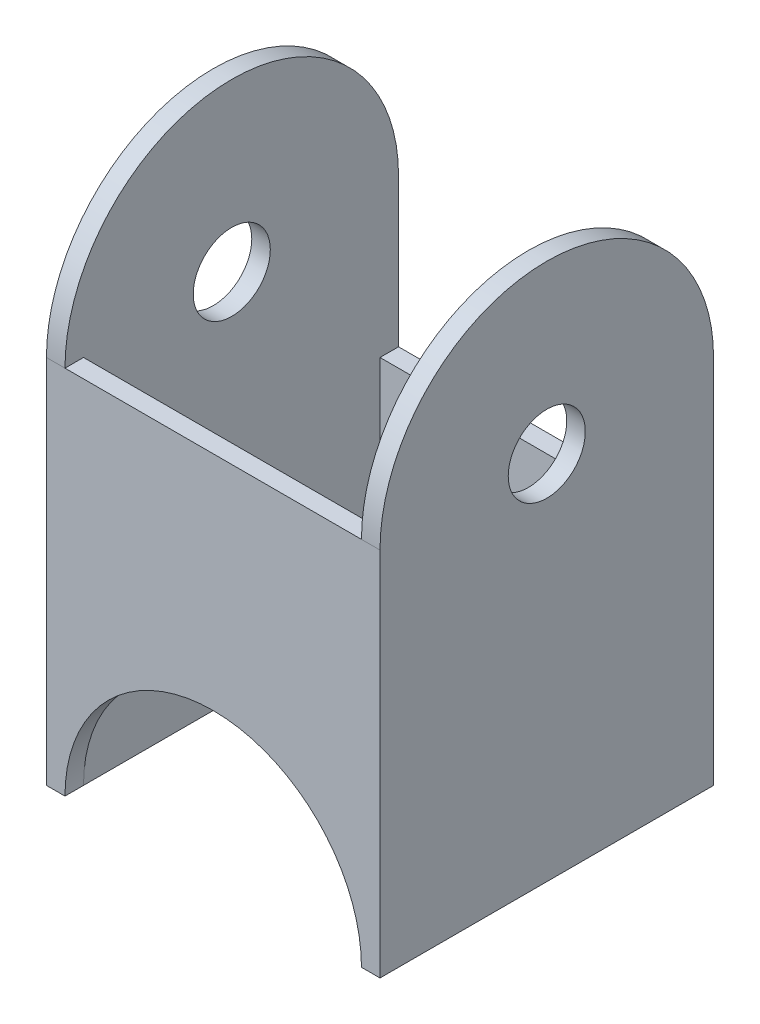
SolidWorks part; units mm, degrees
material "AISI 4130 Steel, annealed at 865C"
ref_plane "Front Plane" through (0, 0, 0) normal (0, 0, 1) x (1, 0, 0)
ref_plane "Top Plane" through (0, 0, 0) normal (0, 1, 0) x (1, 0, 0)
ref_plane "Right Plane" through (0, 0, 0) normal (1, 0, 0) x (0, 0, -1)
sketch "Sketch1" plane through (0, 0, 0) normal (0, 1, 0) x (1, 0, 0)
  line L1 (-12.7, 12.7) -> (12.7, 12.7)
  line L2 (-12.7, 12.7) -> (-12.7, -12.7)
  line L3 (-12.7, -12.7) -> (12.7, -12.7)
  line L4 (12.7, 12.7) -> (12.7, -12.7)
  line L5 (-12.7, 12.7) -> (12.7, -12.7) construction
  line L6 (-12.7, -12.7) -> (12.7, 12.7) construction
  line L7 (-14.2875, 14.2875) -> (14.2875, 14.2875)
  line L8 (-14.2875, 14.2875) -> (-14.2875, -14.2875)
  line L9 (-14.2875, -14.2875) -> (14.2875, -14.2875)
  line L10 (14.2875, 14.2875) -> (14.2875, -14.2875)
  line L11 (-14.2875, 14.2875) -> (14.2875, -14.2875) construction
  line L12 (-14.2875, -14.2875) -> (14.2875, 14.2875) construction
  point P0 (0, 0)
  point P6 (0, 0)
  dimension "D1" = 25.4
  dimension "D2" = 25.4
  dimension "D3" = 1.5875
extrude "Boss-Extrude1" add sketch "Sketch1" along normal blind 31.75
sketch "Sketch2" plane through (-14.2875, 0, 0) normal (-1, 0, 0) x (0, 0, 1)
  line L0 (-14.2875, 31.75) -> (14.2875, 31.75) construction
  circle A0 centre (0, 31.75) radius 14.2875
extrude "Boss-Extrude2" add sketch "Sketch2" against normal up to surface (1.5875 mm away) up to face at (-12.7, 15.875, 0)
sketch "Sketch3" plane through (14.2875, 0, 0) normal (1, 0, 0) x (0, 0, -1)
  line L0 (-14.2875, 31.75) -> (14.2875, 31.75) construction
  circle A0 centre (0, 31.75) radius 14.2875
  arc A1 (14.2875, 31.75) -> (-14.2875, 31.75) centre (0, 31.75) ccw construction
extrude "Boss-Extrude3" add sketch "Sketch3" against normal up to surface (1.5875 mm away) up to face at (12.7, 15.875, 0)
sketch "Sketch4" plane through (-14.2875, 0, 0) normal (-1, 0, 0) x (0, 0, 1)
  circle A0 centre (0, 31.75) radius 3.302
  arc A1 (14.2875, 31.75) -> (-14.2875, 31.75) centre (0, 31.75) ccw construction
  dimension "D1" = 6.604
extrude "Cut-Extrude1" cut sketch "Sketch4" against normal through all both and the other way through all
sketch "Sketch5" plane through (0, 0, 14.2875) normal (0, 0, 1) x (1, 0, 0)
  circle A0 centre (0, 0) radius 12.7
  point P3 (0, 12.7)
  dimension "D1" = 25.4
extrude "Cut-Extrude2" cut sketch "Sketch5" against normal through all both and the other way through all
sketch "Sketch6" plane through (0, 0, -12.7) normal (0, 0, 1) x (1, 0, 0)
  line L0 (12.7, 35.052) -> (12.7, 28.448) construction
  line L1 (-12.7, 31.75) -> (12.7, 31.75)
  line L2 (-12.7, 31.75) -> (-12.7, 19.05)
  line L3 (-12.7, 19.05) -> (12.7, 19.05)
  line L4 (12.7, 31.75) -> (12.7, 19.05)
  line L5 (-12.7, 31.75) -> (12.7, 19.05) construction
  line L6 (-12.7, 19.05) -> (12.7, 31.75) construction
  point P4 (0, 25.4)
  dimension "D1" = 12.7
extrude "Cut-Extrude3" cut sketch "Sketch6" against normal up to next
ref_axis "Axis1" through (14.2875, 31.75, 0) along (-1, 0, 0)
ref_point "Point2"
ref_point "Point4"
